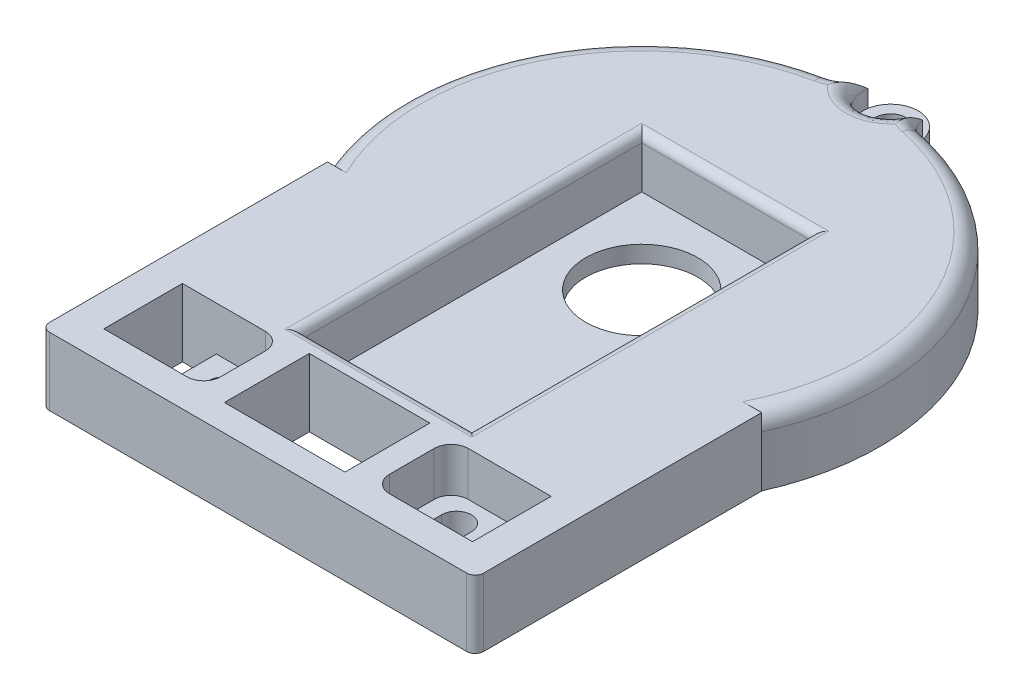
SolidWorks part; units mm, degrees
ref_plane "Alzado" through (0, 0, 0) normal (0, 0, 1) x (1, 0, 0)
ref_plane "Planta" through (0, 0, 0) normal (0, 1, 0) x (1, 0, 0)
ref_plane "Vista lateral" through (0, 0, 0) normal (1, 0, 0) x (0, 0, -1)
sketch "Croquis1" plane through (0, 0, 0) normal (0, 1, 0) x (1, 0, 0)
  line L0 (0, -42.7515) -> (0, 42.7515) construction
  line L1 (25.5551, 15.9364) -> (25.565, 15.9364)
  line L2 (-25.565, -17.8008) -> (25.565, -17.8008)
  line L3 (-25.565, -17.8008) -> (-25.565, 15.9364)
  line L4 (-25.565, 15.9364) -> (-25.5551, 15.9364)
  line L5 (25.565, -17.8008) -> (25.565, 15.9364)
  line L6 (-15.44, -8.1308) -> (-15.44, -11.1308)
  line L7 (-7.1, -4.6708) -> (7.1, -4.6708)
  line L8 (-7.1, -4.6708) -> (-7.1, -14.6708)
  line L9 (-7.1, -14.6708) -> (7.1, -14.6708)
  line L10 (7.1, -4.6708) -> (7.1, -14.6708)
  line L11 (-21.71, -5.0008) -> (-17.71, -5.0008)
  line L12 (-21.71, -5.0008) -> (-21.71, -14.2608)
  line L13 (-21.71, -14.2608) -> (-17.71, -14.2608)
  line L14 (-17.71, -5.0008) -> (-17.71, -14.2608)
  line L15 (17.71, -5.0008) -> (21.71, -5.0008)
  line L16 (17.71, -5.0008) -> (17.71, -14.2608)
  line L17 (17.71, -14.2608) -> (21.71, -14.2608)
  line L18 (21.71, -5.0008) -> (21.71, -14.2608)
  line L19 (-11.94, -11.1308) -> (-11.94, -8.1308)
  line L20 (11.94, -11.1308) -> (11.94, -8.1308)
  line L21 (15.44, -11.1308) -> (15.44, -8.1308)
  arc A0 (25.5551, 15.9364) -> (5.5598, 54.8217) centre (0, 27.3792) ccw
  circle A1 centre (0, 27.3792) radius 6.6
  arc A2 (3.2009, 57.2422) -> (-3.2009, 57.2422) centre (0, 56.6792) ccw
  arc A3 (3.2009, 57.2422) -> (5.5598, 54.8217) centre (6.1555, 57.762) ccw
  arc A4 (-5.5598, 54.8217) -> (-3.2009, 57.2422) centre (-6.1555, 57.762) ccw
  arc A5 (-5.5598, 54.8217) -> (-25.5551, 15.9364) centre (0, 27.3792) ccw
  circle A6 centre (0, 56.6792) radius 1.85
  arc A7 (-11.94, -8.1308) -> (-15.44, -8.1308) centre (-13.69, -8.1308) ccw
  arc A8 (-15.44, -11.1308) -> (-11.94, -11.1308) centre (-13.69, -11.1308) ccw
  arc A9 (15.44, -8.1308) -> (11.94, -8.1308) centre (13.69, -8.1308) ccw
  arc A10 (11.94, -11.1308) -> (15.44, -11.1308) centre (13.69, -11.1308) ccw
  dimension "D2" = 56
  dimension "D6" = 13.2
  dimension "D7" = 6.5
  dimension "D10" = 6
  dimension "D9" = 3.7
  dimension "D22" = 3.5
  dimension "D1" = 51.13
  dimension "D3" = 45.18
  dimension "D4" = 25.565
  dimension "D5" = 33.7372
  dimension "D8" = 29.3
  dimension "D11" = 14.2
  dimension "D12" = 7.1
  dimension "D13" = 10
  dimension "D14" = 32.05
  dimension "D15" = 4
  dimension "D16" = 17.71
  dimension "D17" = 9.26
  dimension "D18" = 32.38
  dimension "D19" = 17.71
  dimension "D20" = 32.38
  dimension "D21" = 3
  dimension "D23" = 35.51
  dimension "D24" = 13.69
  dimension "D25" = 13.69
extrude "Saliente-Extruir1" add sketch "Croquis1" along normal blind 8
sketch "Croquis2" plane through (0, 8, 0) normal (0, 1, 0) x (1, 0, 0)
  line L1 (21.71, -14.2608) -> (11.94, -14.2608)
  line L2 (21.71, -14.2608) -> (21.71, -5.0008)
  line L3 (21.71, -5.0008) -> (11.94, -5.0008)
  line L4 (9.94, -12.2608) -> (9.94, -7.0008)
  line L5 (-21.71, -14.2608) -> (-11.94, -14.2608)
  line L6 (-21.71, -14.2608) -> (-21.71, -5.0008)
  line L7 (-21.71, -5.0008) -> (-11.94, -5.0008)
  line L8 (-9.94, -12.2608) -> (-9.94, -7.0008)
  line L10 (21.71, -5.0008) -> (17.71, -5.0008) construction
  line L11 (11.94, -8.1308) -> (11.94, -11.1308) construction
  line L12 (-21.71, -14.2608) -> (-17.71, -14.2608) construction
  line L13 (-17.71, -5.0008) -> (-21.71, -5.0008) construction
  line L14 (-21.71, -5.0008) -> (-21.71, -14.2608) construction
  line L15 (-11.94, -11.1308) -> (-11.94, -8.1308) construction
  arc A0 (11.94, -5.0008) -> (9.94, -7.0008) centre (11.94, -7.0008) ccw
  arc A1 (11.94, -14.2608) -> (9.94, -12.2608) centre (11.94, -12.2608) cw
  arc A2 (-11.94, -14.2608) -> (-9.94, -12.2608) centre (-11.94, -12.2608) ccw
  arc A3 (-11.94, -5.0008) -> (-9.94, -7.0008) centre (-11.94, -7.0008) cw
  point P9 (21.71, -4.0604)
  point P12 (0, 0)
  point P15 (0, 0)
  point P18 (0, 0)
  point P21 (0, 0)
  dimension "D3" = 2
  dimension "D1" = 2
  dimension "D2" = 2
extrude "Cortar-Extruir1" cut sketch "Croquis2" against normal blind 5.2
sketch "Croquis3" plane through (0, 8, 0) normal (0, 1, 0) x (1, 0, 0)
  line L0 (0, -4.4) -> (0, 4.4) construction
  line L1 (-10, 37.3792) -> (10, 37.3792)
  line L2 (-10, 37.3792) -> (-10, -2.6208)
  line L3 (-10, -2.6208) -> (10, -2.6208)
  line L4 (10, 37.3792) -> (10, -2.6208)
  circle A0 centre (0, 27.3792) radius 6.6 construction
  dimension "D4" = 10
  dimension "D1" = 20
  dimension "D2" = 10
  dimension "D3" = 40
extrude "Cortar-Extruir2" cut sketch "Croquis3" against normal blind 6
fillet "Redondeo1" radius 1 4 edges at (0, 8, 2.6208) (10, 8, -17.3792) (-10, 8, -17.3792) (0, 8, -37.3792)
sketch "Croquis4" plane through (0, 8, 0) normal (0, 1, 0) x (1, 0, 0)
  circle A0 centre (0, 56.6792) radius 3.25
extrude "Cortar-Extruir3" cut sketch "Croquis4" against normal blind 4
fillet "Redondeo2" radius 2 5 edges at (-4.007, 8, -55.6681) (4.007, 8, -55.6681) (-24.9008, 8, -40.1835) (0, 8, -53.4292) (24.9008, 8, -40.1835)
sketch "Croquis5" plane through (0, 8, 0) normal (0, 1, 0) x (1, 0, 0)
  circle A0 centre (0, 27.3792) radius 10
  dimension "D1" = 20
fillet "Redondeo3" radius 1 2 edges at (-25.565, 4, 17.8008) (25.565, 4, 17.8008)
